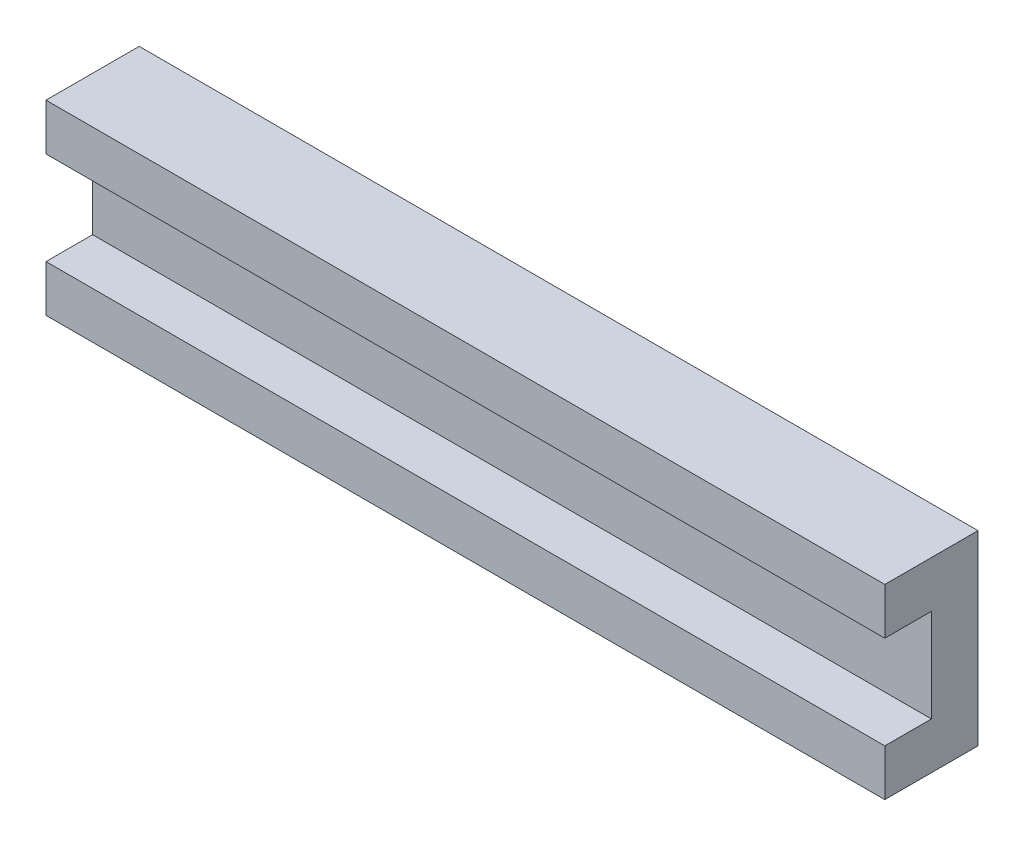
SolidWorks part; units mm, degrees
ref_plane "Front Plane" through (0, 0, 0) normal (0, 0, 1) x (1, 0, 0)
ref_plane "Top Plane" through (0, 0, 0) normal (0, 1, 0) x (1, 0, 0)
ref_plane "Right Plane" through (0, 0, 0) normal (1, 0, 0) x (0, 0, -1)
sketch "Sketch1" plane through (0, 0, 0) normal (0, 0, 1) x (1, 0, 0)
  line L1 (45, 0) -> (45, 10)
  line L2 (45, 10) -> (-45, 10)
  line L3 (-45, 10) -> (-45, 0)
  line L5 (-45, 0) -> (-45, -10)
  line L6 (-45, -10) -> (45, -10)
  line L7 (45, -10) -> (45, 0)
extrude "Boss-Extrude1" add sketch "Sketch1" along normal blind 10
sketch "Sketch2" plane through (0, 0, 0) normal (0, 0, 1) x (1, 0, 0)
  line L1 (0, 5) -> (45, 5)
  line L2 (45, -10) -> (45, 10) construction
  line L3 (45, 5) -> (45, -5)
  line L4 (45, -5) -> (0, -5)
  line L5 (0, -5) -> (-45, -5)
  line L6 (-45, 10) -> (-45, -10) construction
  line L7 (-45, -5) -> (-45, 5)
  line L9 (0, 5) -> (-45, 5)
extrude "Cut-Extrude2" cut sketch "Sketch2" along normal blind 22
extrude "Boss-Extrude2" add sketch "Sketch2<3>" along normal blind 5
sketch "Sketch2<3>" plane through (0, 0, 0) normal (0, 0, 1) x (1, 0, 0) same geometry as "Sketch2"
